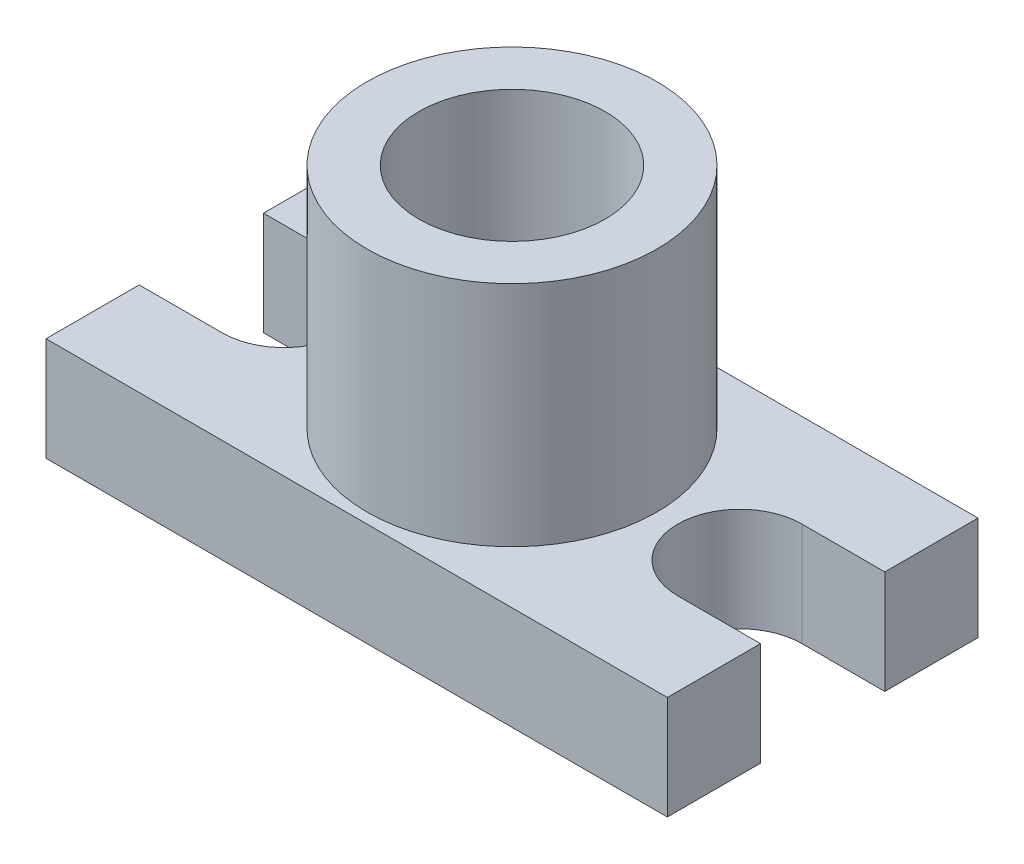
SolidWorks part; units mm, degrees
ref_plane "前视基准面" through (0, 0, 0) normal (0, 0, 1) x (1, 0, 0)
ref_plane "上视基准面" through (0, 0, 0) normal (0, 1, 0) x (1, 0, 0)
ref_plane "右视基准面" through (0, 0, 0) normal (1, 0, 0) x (0, 0, -1)
other "Configuration Table"
sketch "草图2" plane through (0, 0, 0) normal (0, 1, 0) x (1, 0, 0)
  line L0 (-162.5208, 0) -> (7963.5191, 0) construction
  line L1 (-15, -7.5) -> (15, -7.5)
  line L2 (-15, -7.5) -> (-15, -3)
  line L3 (-15, 7.5) -> (15, 7.5)
  line L4 (15, -7.5) -> (15, -3)
  line L5 (-15, -7.5) -> (15, 7.5) construction
  line L6 (-15, 7.5) -> (15, -7.5) construction
  line L7 (0, -162.5208) -> (0, 7963.5191) construction
  line L8 (-11, 3) -> (-15, 3)
  line L9 (-11, -3) -> (-15, -3)
  line L10 (-15, 3) -> (-15, 7.5)
  line L11 (11, -3) -> (15, -3)
  line L12 (11, 3) -> (15, 3)
  line L13 (15, 3) -> (15, 7.5)
  arc A0 (-11, -3) -> (-11, 3) centre (-11, 0) ccw
  arc A1 (11, -3) -> (11, 3) centre (11, 0) cw
  point P0 (0, 0)
  dimension "D4" = 3
  dimension "D1" = 30
  dimension "D2" = 22
  dimension "D3" = 15
extrude "凸台-拉伸1" add sketch "草图2" along normal blind 5
sketch "草图3" plane through (0, 5, 0) normal (0, 1, 0) x (1, 0, 0)
  circle A0 centre (0, 0) radius 4.5
  circle A1 centre (0, 0) radius 7
  dimension "D1" = 9
  dimension "D2" = 14
extrude "凸台-拉伸2" add sketch "草图3" along normal blind 11
extrude "切除-拉伸1" cut sketch "草图3<3>" against normal through all contours A0
sketch "草图3<3>" plane through (0, 5, 0) normal (0, 1, 0) x (1, 0, 0) same geometry as "草图3"
